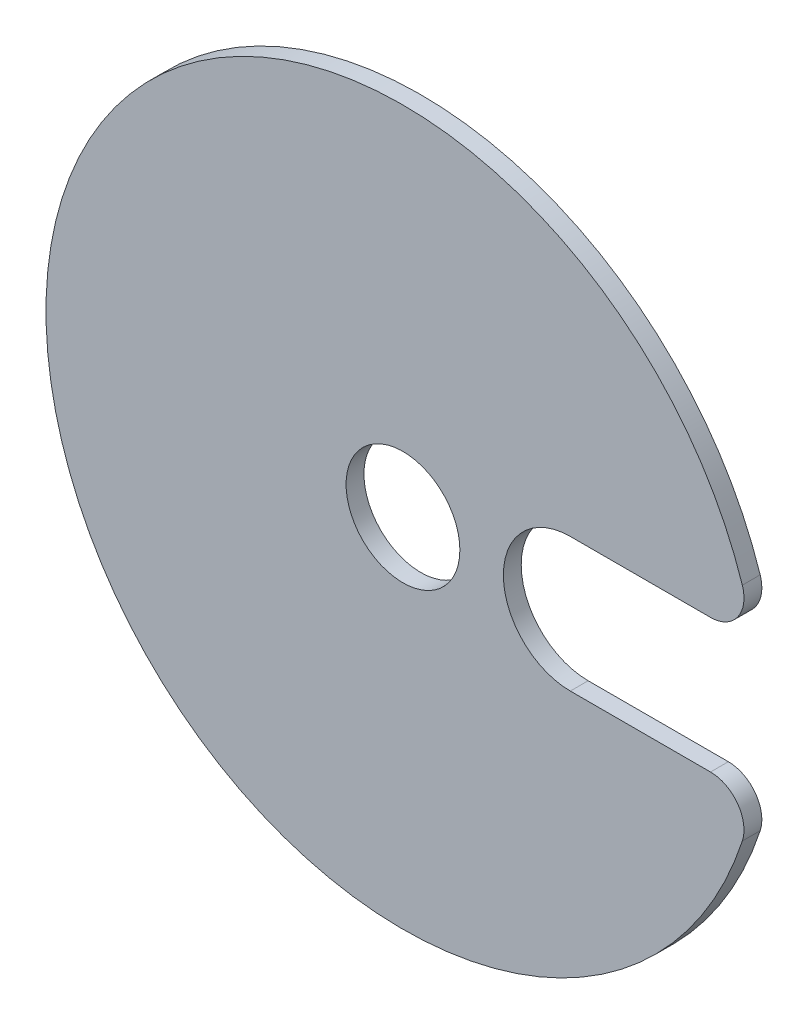
SolidWorks part; units mm, degrees
ref_plane "Plan de face" through (0, 0, 0) normal (0, 0, 1) x (1, 0, 0)
ref_plane "Plan de dessus" through (0, 0, 0) normal (0, 1, 0) x (1, 0, 0)
ref_plane "Plan de droite" through (0, 0, 0) normal (1, 0, 0) x (0, 0, -1)
sketch "Esquisse1" plane through (0, 0, 0) normal (0, 0, 1) x (1, 0, 0)
  line L0 (31.4325, 6) -> (15, 6)
  line L1 (0, 0) -> (23.2256, 0) construction
  line L2 (31.4325, -6) -> (15, -6)
  circle A0 centre (0, 0) radius 5.1
  arc A1 (15, 6) -> (15, -6) centre (15, 0) ccw
  arc A2 (31.4325, 6) -> (31.4325, -6) centre (0, 0) ccw
  point P10 (-0.6699, 0)
  dimension "D1" = 10.2
  dimension "D3" = 32
  dimension "D2" = 12
  dimension "D4" = 15
extrude "Boss.-Extru.1" add sketch "Esquisse1" along normal blind 1.6
fillet "Congé1" radius 3 2 edges at (31.4325, -6, 0.8) (31.4325, 6, 0.8)
